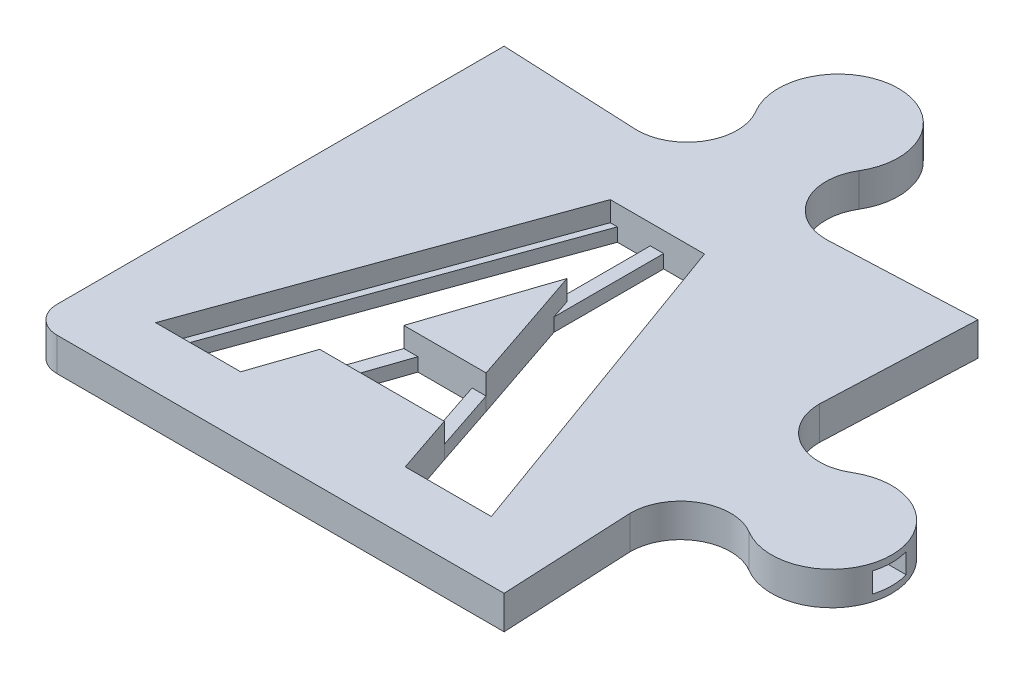
SolidWorks part; units mm, degrees
ref_plane "Front Plane" through (0, 0, 0) normal (0, 0, 1) x (1, 0, 0)
ref_plane "Top Plane" through (0, 0, 0) normal (0, 1, 0) x (1, 0, 0)
ref_plane "Right Plane" through (0, 0, 0) normal (1, 0, 0) x (0, 0, -1)
sketch "Sketch1" plane through (0, 0, 0) normal (0, 1, 0) x (1, 0, 0)
  line L0 (-31, -36) -> (37, -36) construction
  line L1 (-36, 37) -> (-36, -31) construction
  line L2 (-14.1421, 36) -> (-36, 37) construction
  line L3 (37, 37) -> (14.1421, 36) construction
  line L4 (36, 13.1421) -> (37, 37) construction
  line L5 (37, -36) -> (36, -15.1421) construction
  line L6 (-35, 35.9532) -> (-35, -31)
  line L7 (-36, 36) -> (36, 36) construction
  line L8 (-36, 36) -> (-36, -36) construction
  line L9 (-36, -36) -> (36, -36) construction
  line L10 (36, 36) -> (36, -36) construction
  line L11 (-31, -35) -> (35.9509, -35)
  line L12 (35.9509, -35) -> (35, -15.1669)
  line L13 (35, 13.1638) -> (35.9553, 35.9533)
  line L14 (35.9553, 35.9533) -> (14.1648, 35)
  line L15 (-14.1658, 35) -> (-35, 35.9532)
  line L16 (-30, -24) -> (30, -24) construction
  line L17 (-30, 29) -> (30, 29) construction
  line L18 (-30, 29) -> (-30, -31) construction
  line L19 (-30, -31) -> (30, -31) construction
  line L20 (30, 29) -> (30, -31) construction
  line L21 (-30, 24) -> (30, 24) construction
  line L22 (-30, 24) -> (-30, -26) construction
  line L23 (-30, -26) -> (30, -26) construction
  line L24 (30, 24) -> (30, -26) construction
  arc A0 (-36, -31) -> (-31, -36) centre (-31, -31) ccw construction
  arc A1 (-14.1421, 36) -> (-8.571, 45.8485) centre (-14.1421, 42.5) ccw construction
  arc A2 (8.571, 45.8485) -> (-8.571, 45.8485) centre (0, 51) ccw construction
  arc A3 (8.571, 45.8485) -> (14.1421, 36) centre (14.1421, 42.5) ccw construction
  arc A4 (36, 13.1421) -> (45.8485, 7.571) centre (42.5, 13.1421) ccw construction
  arc A5 (45.8485, -9.571) -> (45.8485, 7.571) centre (51, -1) ccw construction
  arc A6 (45.8485, -9.571) -> (36, -15.1421) centre (42.5, -15.1421) ccw construction
  arc A7 (-35, -31) -> (-31, -35) centre (-31, -31) ccw
  arc A8 (46.3636, -8.7139) -> (35, -15.1669) centre (42.5, -15.1421) ccw
  arc A9 (46.3636, -8.7139) -> (46.3636, 6.7139) centre (51, -1) ccw
  arc A10 (35, 13.1638) -> (46.3636, 6.7139) centre (42.5, 13.1421) ccw
  arc A11 (7.7139, 46.3636) -> (14.1648, 35) centre (14.1421, 42.5) ccw
  arc A12 (7.7139, 46.3636) -> (-7.7139, 46.3636) centre (0, 51) ccw
  arc A13 (-14.1658, 35) -> (-7.7139, 46.3636) centre (-14.1421, 42.5) ccw
  point P32 (36, 0)
  point P34 (0, 36)
  dimension "D5" = 6.5
  dimension "D6" = 10
  dimension "D7" = 6.5
  dimension "D13" = 5
  dimension "D9" = 10
  dimension "D11" = 6.5
  dimension "D12" = 6.5
  dimension "D1" = 72
  dimension "D2" = 1
  dimension "D3" = 1
  dimension "D4" = 15
  dimension "D8" = 1
  dimension "D10" = 35
  dimension "D14" = 15
  dimension "D15" = 36
  dimension "D16" = 1
  dimension "D18" = 60
  dimension "D19" = 60
  dimension "D20" = 5
  dimension "D21" = 6
  dimension "D22" = 5
  dimension "D23" = 50
  dimension "D24" = 2
  dimension "D17" = 1
extrude "Boss-Extrude1" add sketch "Sketch1" along normal blind 5
sketch "Sketch3" plane through (0, 5, 0) normal (0, 1, 0) x (1, 0, 0)
  text T0 "A" font "Poppins" height 50
extrude "Cut-Extrude1" cut sketch "Sketch3" against normal blind 3
sketch "Sketch4" plane through (0, 2, 0) normal (0, 1, 0) x (1, 0, 0)
  line L0 (-0.1649, 10.5416) -> (-0.1649, 24) construction
  line L1 (-30, 24) -> (30, 24) construction
  line L2 (-0.1649, 10.5416) -> (-6.2964, -7.7704) construction
  line L3 (-1.1599, 7.5701) -> (0.8401, 7.5701)
  line L4 (-1.1599, 7.5701) -> (-1.1599, 24)
  line L5 (-1.1599, 24) -> (0.8401, 24)
  line L6 (0.8401, 7.5701) -> (0.8401, 24)
  line L7 (6.0284, -7.7704) -> (-0.1649, 10.5416) construction
  line L8 (-9.5012, -17.1686) -> (-6.2964, -7.7704)
  line L9 (-6.2964, -7.7704) -> (-4.1833, -7.7704)
  line L10 (-6.2964, -7.7704) -> (6.0284, -7.7704) construction
  line L11 (-4.1833, -7.7704) -> (-7.3881, -17.1686)
  line L12 (9.1612, -17.1686) -> (-9.5012, -17.1686) construction
  line L13 (-7.3881, -17.1686) -> (-9.5012, -17.1686)
  line L14 (6.0284, -7.7704) -> (9.1612, -17.1686)
  line L15 (9.1612, -17.1686) -> (7.053, -17.1686)
  line L16 (9.1612, -17.1686) -> (-9.5012, -17.1686) construction
  line L17 (7.053, -17.1686) -> (3.9203, -7.7704)
  line L18 (-6.2964, -7.7704) -> (6.0284, -7.7704) construction
  line L19 (3.9203, -7.7704) -> (6.0284, -7.7704)
  line L20 (-6.0883, 24) -> (-24.1736, -26)
  line L21 (-30, -26) -> (30, -26) construction
  line L22 (5.8925, 24) -> (23.9778, -26)
  line L23 (6.9559, 24) -> (25.0412, -26) construction
  line L24 (-25.237, -26) -> (-7.1517, 24) construction
  line L25 (-25.237, -26) -> (-7.1517, 24) construction
  line M14 (-6.2964, -7.7704) -> (-0.1649, 10.5416)
  line M15 (-0.1649, 10.5416) -> (6.0284, -7.7704)
  line M16 (6.0284, -7.7704) -> (-6.2964, -7.7704)
  line M17 (9.1612, -17.1686) -> (12.1496, -26)
  line M18 (12.1496, -26) -> (25.0412, -26)
  line M19 (25.0412, -26) -> (6.9559, 24)
  line M20 (6.9559, 24) -> (-7.1517, 24)
  line M21 (-7.1517, 24) -> (-25.237, -26)
  line M22 (-25.237, -26) -> (-12.4897, -26)
  line M23 (-12.4897, -26) -> (-9.5012, -17.1686)
  line M24 (-9.5012, -17.1686) -> (9.1612, -17.1686)
  dimension "D1" = 2
  dimension "D2" = 2
  dimension "D3" = 2
  dimension "D4" = 1
  dimension "D5" = 1
extrude "Cut-Extrude2" cut sketch "Sketch4" against normal through all contours L17 L11 M24 M16 | L14 L6 M15 M17 M18 M19 M20 | L8 L4 M23 M14 M20 M21 M22 region at (-10.681, 2, 3.2498) region at (10.4215, 2, 3.228) region at (-0.1512, 2, 12.9098)
sketch "Sketch6" plane through (0, 0, 0) normal (0, -1, 0) x (1, 0, 0)
  line L0 (-35, -35.9532) -> (-35, 31) construction
  line L1 (-35, 18) -> (-27, 18)
  line L2 (-35, 18) -> (-35, -16)
  line L3 (-35, -16) -> (-27, -16)
  line L4 (-27, 18) -> (-27, -16)
  line L5 (-31, 35) -> (35.9509, 35) construction
  line L6 (-35, 14.75) -> (-30, 14.75)
  line L7 (-35, 14.75) -> (-35, -12.75)
  line L8 (-35, -12.75) -> (-30, -12.75)
  line L9 (-30, 14.75) -> (-30, -12.75)
  point P14 (0, 0)
  point P15 (-27, 1)
  point P16 (-30, 1)
  line M28 (-35, 31) -> (-35, -35.9532)
  dimension "D1" = 8
  dimension "D2" = 20.25
  dimension "D3" = 27.5
  dimension "D4" = 5
  dimension "D5" = 34
extrude "Cut-Extrude3" cut sketch "Sketch6" against normal blind 3 from offset 1 contours L6 L9 L8 L3 L4 L1 M28 | L9 L6 L2 L8 region at (-29.4665, 0, 1) region at (-32.5, 0, 1) offset against normal yes
extrude "Cut-Extrude4" cut sketch "Sketch6<3>" against normal up to next contours L9 L6 L2 L8 region at (-32.5, 0, 1)
sketch "Sketch6<3>" plane through (0, 0, 0) normal (0, -1, 0) x (1, 0, 0) same geometry as "Sketch6"
sketch "Sketch8" plane through (0, 0, 0) normal (0, -1, 0) x (1, 0, 0)
  line L1 (-2.5, -51) -> (2.5, -51)
  line L2 (-2.5, -51) -> (-2.5, -60)
  line L3 (-2.5, -60) -> (2.5, -60)
  line L4 (2.5, -51) -> (2.5, -60)
  line L5 (51, 3.5) -> (60, 3.5)
  line L6 (51, 3.5) -> (51, -1.5)
  line L7 (51, -1.5) -> (60, -1.5)
  line L8 (60, 3.5) -> (60, -1.5)
  arc A0 (-7.7139, -46.3636) -> (7.7139, -46.3636) centre (0, -51) ccw construction
  arc A1 (46.3636, -6.7139) -> (46.3636, 8.7139) centre (51, 1) ccw construction
  point P4 (0, -60)
  point P13 (60, 1)
  dimension "D1" = 5
  dimension "D2" = 9
  dimension "D3" = 5
  dimension "D4" = 9
extrude "Cut-Extrude5" cut sketch "Sketch8" against normal blind 3 from offset 1 offset against normal yes
